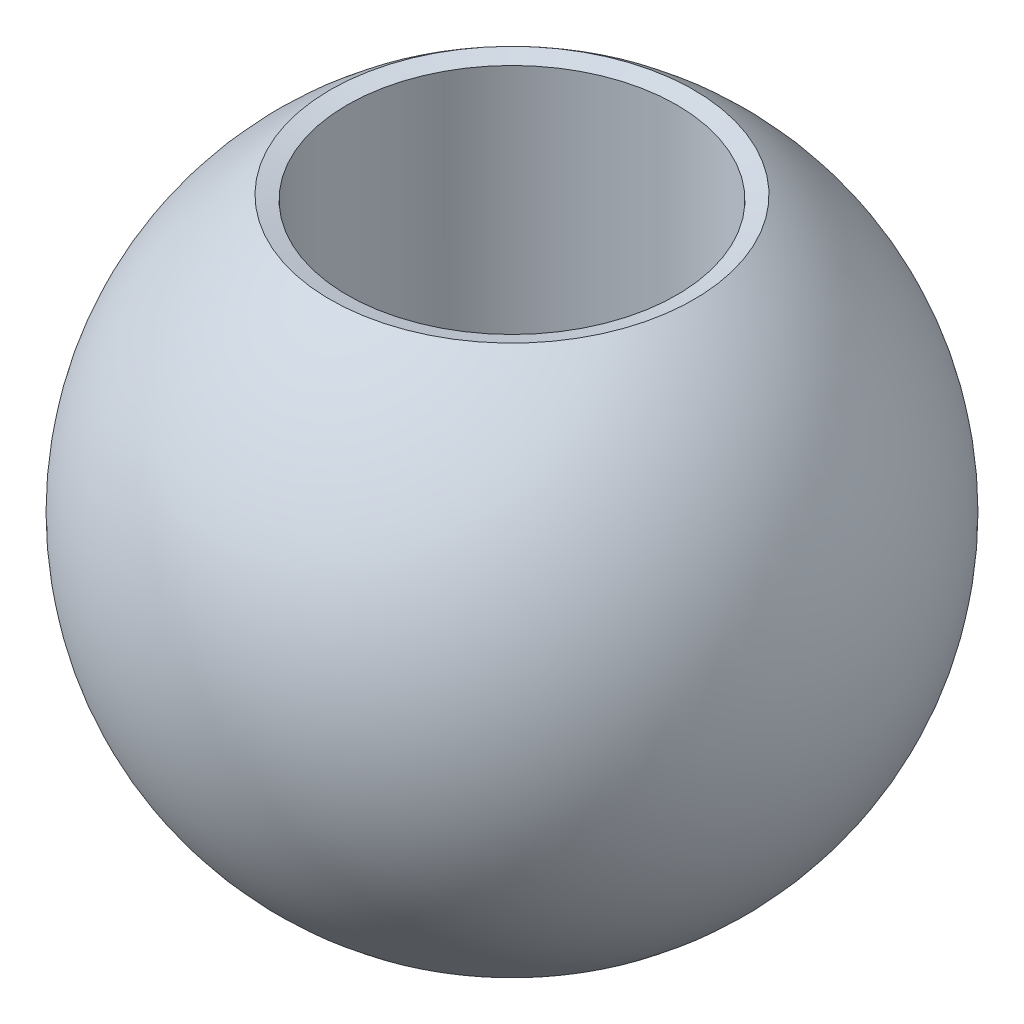
SolidWorks part; units mm, degrees
material "Acero inoxidable al cromo"
ref_plane "Alzado" through (0, 0, 0) normal (0, 0, 1) x (1, 0, 0)
ref_plane "Planta" through (0, 0, 0) normal (0, 1, 0) x (1, 0, 0)
ref_plane "Vista lateral" through (0, 0, 0) normal (1, 0, 0) x (0, 0, -1)
sketch "Croquis1" plane through (0, 0, 0) normal (0, 0, 1) x (1, 0, 0)
  line L0 (0, -8) -> (0, 8)
  line L1 (0, 0) -> (4, 0)
  arc A0 (0, 8) -> (0, -8) centre (0, 0) cw
  dimension "D1" = 8
revolve "Revolución1" add sketch "Croquis1" angle 360 about L0 region at (0.1789, -4, 0)
sketch "Croquis3" plane through (0, 0, 0) normal (0, 1, 0) x (1, 0, 0)
  circle A0 centre (0, 0) radius 4
extrude "Cortar-Extruir1" cut sketch "Croquis3" against normal blind 10 and the other way blind 10
chamfer "Chaflán1" distance 0.5 angle 45 2 edges at (0, 6.9282, -4) (0, -6.9282, 4) first distance on face at (0, 6.9282, -4)
